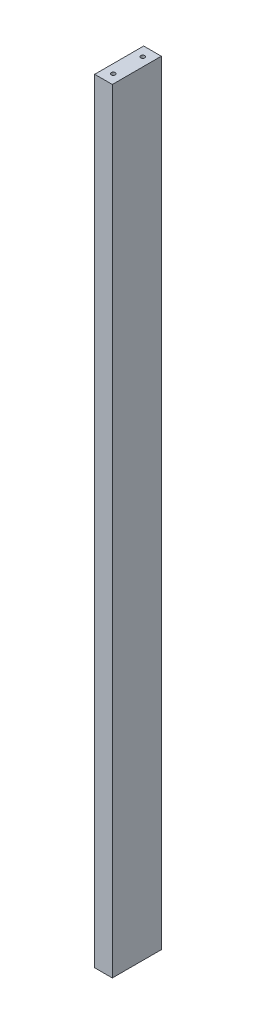
SolidWorks part; units mm, degrees
material "Beech"
ref_plane "Front Plane" through (0, 0, 0) normal (0, 0, 1) x (1, 0, 0)
ref_plane "Top Plane" through (0, 0, 0) normal (0, 1, 0) x (1, 0, 0)
ref_plane "Right Plane" through (0, 0, 0) normal (1, 0, 0) x (0, 0, -1)
sketch "Sketch1" plane through (0, 0, 0) normal (0, 1, 0) x (1, 0, 0)
  line L1 (0, 0) -> (18, 0)
  line L2 (0, 0) -> (0, 50)
  line L3 (0, 50) -> (18, 50)
  line L4 (18, 0) -> (18, 50)
  dimension "D1" = 18
  dimension "D2" = 50
extrude "base" add sketch "Sketch1" along normal blind 789.8
hole_wizard "end bolt holes for inserts" positions "Sketch2" profile "Sketch3" tap size "M5x0.8" standard "ANSI Metric"
sketch "Sketch2" plane through (0, 0, 0) normal (0, -1, 0) x (-1, 0, 0)
  line L1 (-9, 50) -> (-9, 0)
  line L2 (-18, 50) -> (0, 50) construction
  line L3 (0, 0) -> (-18, 0) construction
  line L4 (-9, 10) -> (-18, 25)
  line L5 (-18, 0) -> (-18, 50) construction
  line L6 (-18, 25) -> (-9, 40)
  point P10 (-9, 40)
  point P12 (-9, 10)
  dimension "D1" = 30
sketch "Sketch3" plane through (9, 0, -40) normal (1, 0, 0) x (0, 0, -1)
  line L0 (0, 0) -> (0, 15.2618)
  line L1 (0, 15.2618) -> (2.1, 14)
  line L2 (2.1, 14) -> (2.1, 0)
  line L5 (2.1, 0) -> (0, 0)
  line L10 (0, 15.2618) -> (-2.1, 14) construction
  line L11 (0, -6.35) -> (0, 107.95) construction
  dimension "Tap Drill Dia." = 4.2
  dimension "Tap Drill Depth" = 14
  dimension "Drill Angle" = 118
cosmetic thread "Hole Thread1" parameters "D1"=10, "D2"=5
cosmetic thread "Hole Thread2" parameters "D1"=10, "D2"=5
ref_plane "midplane along length" through (0, 394.9, 0) normal (0, -1, 0) x (-1, 0, 0)
mirror "mirror end bolt holes" about plane through (0, 394.9, 0) normal (0, -1, 0) of "end bolt holes for inserts"
equation "\"board_thickness\" = 18mm"
equation "\"way_width\"= 75mm"
equation "\"way_thickness\"= 50mm"
equation "\"radial_clearance\"= 0.1mm"
equation "\"slider_width\"= \"way_width\"-2* \"radial_clearance\""
equation "\"slider_thickness\" = \"way_thickness\" - 2 * \"radial_clearance\""
equation "\"column_width\"= \"way_width\" + 2 * \"board_thickness\""
equation "\"boxway_slot_width\" = 50mm"
equation "\"keeper_rail_width\" = (\"column_width\" - \"boxway_slot_width\")/2"
equation "\"slider_length\" = 125mm"
equation "\"nut_diameter\"= 22mm"
equation "\"nut_length\"= 15mm"
equation "\"leadscrew_diameter\"= 10mm"
equation "\"leadscrew_radial_clearance\"= 1mm"
equation "\"bearing_bolt_pattern_width\" = 35mm"
equation "\"bearing_bolt_pattern_height\" = 60mm"
equation "\"desktop_bolt_pattern_width\" = 30mm"
equation "\"desktop_bolt_pattern_height\" = 30mm"
equation "\"bearing_bolt_nut_counterbore_diameter\" = 12mm"
equation "\"bearing_bolt_nut_counterbore_depth\"= 10mm"
equation "\"desktop_depth\"= 500mm"
equation "\"desktop_width\"= 650mm"
equation "\"desktop_thickness\"= 18mm"
equation "\"leg_height\"=100mm"
equation "\"leg_width\"=18mm"
equation "\"leg_length\"=500mm"
equation "\"lap_joint_height\" = 50mm"
equation "\"lap_dowel_diameter\"= 8mm"
equation "\"lap_dowel_hole_z_spacing\"=30"
equation "\"D1@Sketch1\"=\"board_thickness\""
equation "\"D2@Sketch1\"=\"lap_joint_height\""
equation "\"D1@Sketch2\"=\"lap_dowel_hole_z_spacing\""
